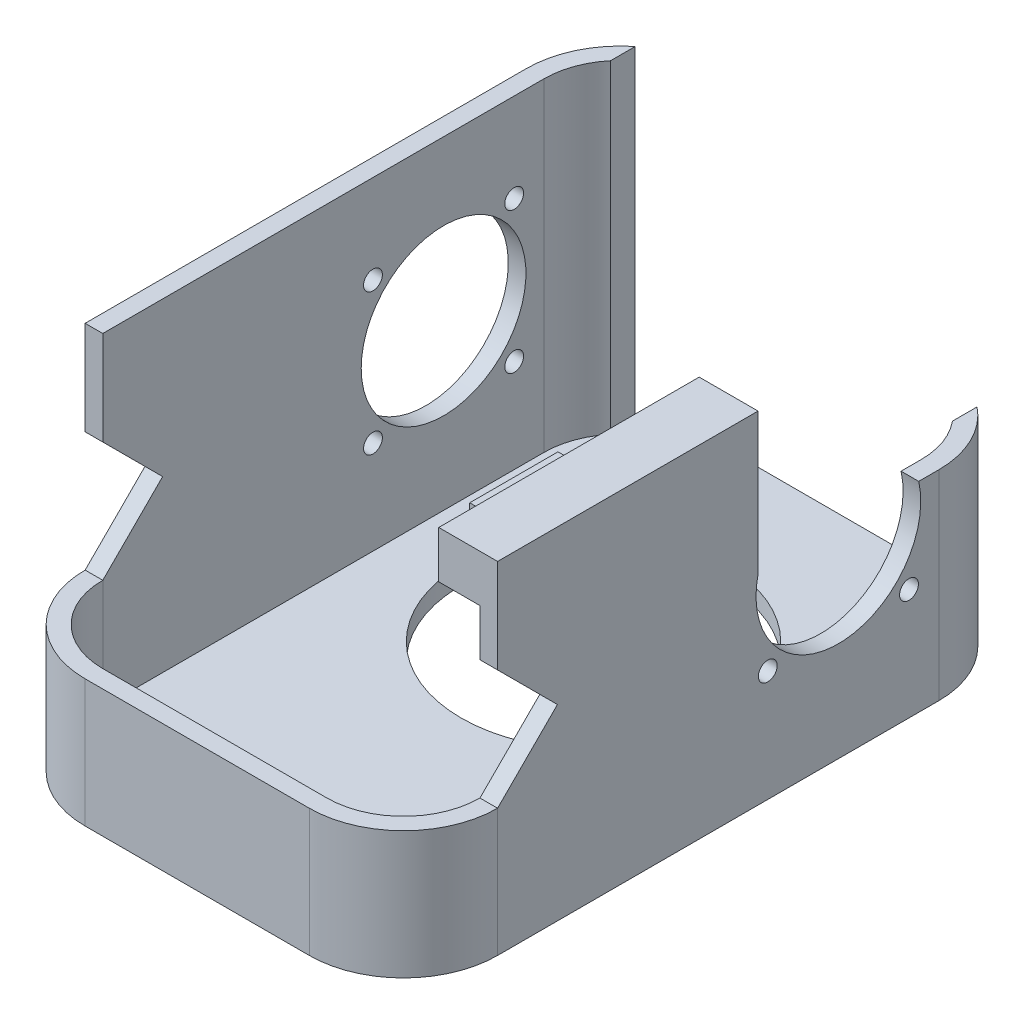
SolidWorks part; units mm, degrees
ref_plane "Front Plane" through (0, 0, 0) normal (0, 0, 1) x (1, 0, 0)
ref_plane "Top Plane" through (0, 0, 0) normal (0, 1, 0) x (1, 0, 0)
ref_plane "Right Plane" through (0, 0, 0) normal (1, 0, 0) x (0, 0, -1)
sketch "Sketch1" plane through (0, 0, 0) normal (0, 1, 0) x (1, 0, 0)
  line L1 (0, 0) -> (64.1, 0)
  line L2 (0, 0) -> (0, 75)
  line L3 (0, 75) -> (64.1, 75)
  line L4 (64.1, 0) -> (64.1, 75)
  line L5 (0, 75) -> (-3, 75)
  line L6 (0, 75) -> (0, 0)
  line L7 (0, 0) -> (-3, 0)
  line L8 (-3, 75) -> (-3, 0)
  line L9 (64.1, 75) -> (67.1, 75)
  line L10 (64.1, 75) -> (64.1, 0)
  line L11 (64.1, 0) -> (67.1, 0)
  line L12 (67.1, 75) -> (67.1, 0)
  line L21 (-3, 75) -> (67.1, 75)
  line L22 (-3, 75) -> (-3, 91)
  line L23 (-3, 91) -> (67.1, 91)
  line L24 (67.1, 75) -> (67.1, 91)
  line L25 (-3, 0) -> (67.1, 0)
  line L26 (-3, 0) -> (-3, -16)
  line L27 (-3, -16) -> (67.1, -16)
  line L28 (67.1, 0) -> (67.1, -16)
  dimension "D1" = 64.1
  dimension "D2" = 75
  dimension "D3" = 3
  dimension "D4" = 3
  dimension "D5" = 16
  dimension "D6" = 16
extrude "Boss-Extrude1" add sketch "Sketch1" along normal blind 3 contours L9 L24 L23 L22 L5 L3 | L1 L4 L3 L2 | L28 L11 L1 L7 L26 L27 region at (32.05, 0, -37.5) region at (32.05, 0, 8) region at (32.05, 0, -83)
extrude "Boss-Extrude2" add sketch "Sketch1<4>" along normal blind 58 contours L12 L9 L4 L11 | L5 L8 L7 L2 region at (-1.5, 0, -37.5) region at (65.6, 0, -37.5)
sketch "Sketch1<4>" plane through (0, 0, 0) normal (0, 1, 0) x (1, 0, 0) same geometry as "Sketch1"
sketch "Sketch2" plane through (0, 0, 0) normal (0, -1, 0) x (1, 0, 0)
  line L0 (32.05, 16) -> (32.05, -91) construction
  line L3 (6.2202, -39.3099) -> (57.8798, -63.3991) construction
  line L5 (-3, -91) -> (67.1, -91) construction
  line L6 (-3, 16) -> (67.1, 16) construction
  circle A0 centre (32.05, -51.3545) radius 22.5
  point P13 (32.05, -51.3545)
  dimension "D1" = 45
  dimension "D2" = 57
  dimension "D3" = 65
extrude "Cut-Extrude1" cut sketch "Sketch2" against normal blind 10
sketch "Sketch3" plane through (0, 0, 0) normal (0, -1, 0) x (1, 0, 0)
  point P0 (57.8798, -63.3991)
  point P2 (6.2202, -39.3099)
fillet "Fillet2" radius 16 4 edges at (-3, 1.5, -91) (67.1, 1.5, -91) (67.1, 1.5, 16) (-3, 1.5, 16)
sketch "Sketch6" plane through (0, 3, 0) normal (0, 1, 0) x (1, 0, 0)
  line L0 (3, 83.3066) -> (3, 87.49)
  line L1 (0, 0) -> (0, 75) construction
  line L2 (61.1, 87.49) -> (61.1, 83.3066)
  line L3 (64.1, 0) -> (64.1, 75) construction
  line L6 (64.1, 0) -> (67.1, 0)
  line L7 (-3, 0) -> (0, 0)
  line L9 (13, -13) -> (51.1, -13)
  line L11 (13, -16) -> (51.1, -16)
  line L17 (-3, 75) -> (0, 75)
  line L20 (64.1, 75) -> (67.1, 75)
  arc A0 (51.1, -16) -> (67.1, 0) centre (51.1, 0) ccw construction
  arc A1 (-3, 0) -> (13, -16) centre (13, 0) ccw construction
  arc A2 (51.1, -16) -> (67.1, 0) centre (51.1, 0) ccw
  arc A3 (-3, 0) -> (13, -16) centre (13, 0) ccw
  arc A4 (0, 0) -> (13, -13) centre (13, 0) ccw
  arc A5 (51.1, -13) -> (64.1, 0) centre (51.1, 0) ccw
  arc A11 (13, 88) -> (0, 75) centre (13, 75) ccw
  arc A12 (3, 83.3066) -> (0, 75) centre (13, 75) ccw
  arc A13 (67.1, 75) -> (51.1, 91) centre (51.1, 75) ccw construction
  arc A14 (64.1, 75) -> (51.1, 88) centre (51.1, 75) ccw
  arc A15 (64.1, 75) -> (61.1, 83.3066) centre (51.1, 75) ccw
  arc A16 (13, 91) -> (-3, 75) centre (13, 75) ccw construction
  arc A17 (67.1, 75) -> (61.1, 87.49) centre (51.1, 75) ccw
  arc A18 (3, 87.49) -> (-3, 75) centre (13, 75) ccw
  point P5 (3, 83.3066)
  dimension "D3" = 3
  dimension "D4" = 3
  dimension "D1" = 3
  dimension "D2" = 3
  dimension "D5" = 3
extrude "Boss-Extrude3" add sketch "Sketch6" along normal up to surface (55 mm away) up to face at (-1.5, 58, -37.5)
sketch "Sketch5" plane through (-3, 0, 0) normal (-1, 0, 0) x (0, 0, 1)
  line L0 (-57.9207, 42.9126) -> (-57.9207, 18.9126) construction
  line L1 (-69.9207, 42.9126) -> (-45.9207, 42.9126) construction
  line L2 (-69.9207, 42.9126) -> (-69.9207, 18.9126) construction
  line L3 (-69.9207, 18.9126) -> (-45.9207, 18.9126) construction
  line L4 (-45.9207, 42.9126) -> (-45.9207, 18.9126) construction
  line L5 (-69.9207, 30.9126) -> (-45.9207, 30.9126) construction
  line L6 (0, 42.0245) -> (-10.1749, 31.8496)
  line L8 (-10.1749, 31.8496) -> (0, 21.6747)
  line L10 (0, 31.8496) -> (-10.1749, 31.8496) construction
  line L11 (0, 42.0245) -> (23.8598, 42.0245)
  line L14 (0, 21.6747) -> (23.8598, 21.6747)
  line L15 (23.8598, 42.0245) -> (23.8598, 21.6747)
  line L16 (0, 42.0245) -> (0, 64.277)
  line L17 (0, 64.277) -> (23.8598, 64.277)
  line L18 (23.8598, 64.277) -> (23.8598, 42.0245)
  circle A0 centre (-57.9207, 30.9126) radius 14
  circle A1 centre (-69.9207, 42.9126) radius 1.6
  circle A2 centre (-69.9207, 18.9126) radius 1.6
  circle A3 centre (-45.9207, 18.9126) radius 1.6
  circle A4 centre (-45.9207, 42.9126) radius 1.6
  line M7 (0, 0) -> (0, 58)
  dimension "D3" = 28
  dimension "D4" = 3.2
  dimension "D5" = 3.2
  dimension "D1" = 24
  dimension "D2" = 24
  dimension "D6" = 135
extrude "Cut-Extrude2" cut sketch "Sketch5" against normal through all contours A0 | A3 | A4 | A1 | A2
sketch "Sketch7" plane through (67.1, 0, 0) normal (1, 0, 0) x (0, 0, -1)
  line L0 (75, 58) -> (0, 58) construction
  line L1 (44.2654, 58) -> (87.49, 58)
  line L2 (44.2654, 58) -> (44.2654, 34)
  line L3 (44.2654, 34) -> (87.49, 34)
  line L4 (87.49, 58) -> (87.49, 34)
  line L5 (87.49, 58) -> (87.49, 3) construction
  circle A0 centre (57.9207, 30.9126) radius 14 construction
  dimension "D1" = 24
extrude "Cut-Extrude3" cut sketch "Sketch7" against normal blind 10
extrude "Cut-Extrude5" cut sketch "Sketch5<5>" against normal blind 74 contours L18 L17 L16 L11 M7 | L15 L11 L14 M7 | L6 L8 M7 region at (-3, 31.8496, -3.3916) region at (-3, 53.1507, 11.9299) region at (-3, 31.8496, 11.9299)
sketch "Sketch5<5>" plane through (-3, 0, 0) normal (-1, 0, 0) x (0, 0, 1) same geometry as "Sketch5"
sketch "Sketch9" plane through (64.1, 0, 0) normal (-1, 0, 0) x (0, 0, 1)
  line L0 (0, 58) -> (0, 42.0245) construction
  line L1 (-44.2654, 58) -> (0, 58)
  line L2 (-44.2654, 58) -> (-44.2654, 50)
  line L3 (-44.2654, 50) -> (0, 50)
  line L4 (0, 58) -> (0, 50)
  line L5 (-44.2654, 34) -> (-44.2654, 58) construction
  line L6 (-29.2654, 50) -> (-14.2654, 50)
  line L7 (-29.2654, 50) -> (-29.2654, 47)
  line L8 (-29.2654, 47) -> (-14.2654, 47)
  line L9 (-14.2654, 50) -> (-14.2654, 47)
  point P11 (0, 47)
  point P12 (0, 0)
  line M11 (0, 42.0245) -> (0, 58)
  line M12 (0, 58) -> (-44.2654, 58)
  line M13 (-44.2654, 58) -> (-44.2654, 34)
  dimension "D1" = 8
  dimension "D2" = 3
  dimension "D3" = 15
  dimension "D4" = 15
extrude "Boss-Extrude4" add sketch "Sketch9" along normal blind 7 contours L3 M13 M11 M12 region at (64.1, 54, -22.1327)
extrude "Boss-Extrude5" add sketch "Sketch9<4>" along normal blind 16 contours L7 L8 L3 M11 region at (64.1, 48.5, -21.7654)
sketch "Sketch9<4>" plane through (64.1, 0, 0) normal (-1, 0, 0) x (0, 0, 1) same geometry as "Sketch9"
